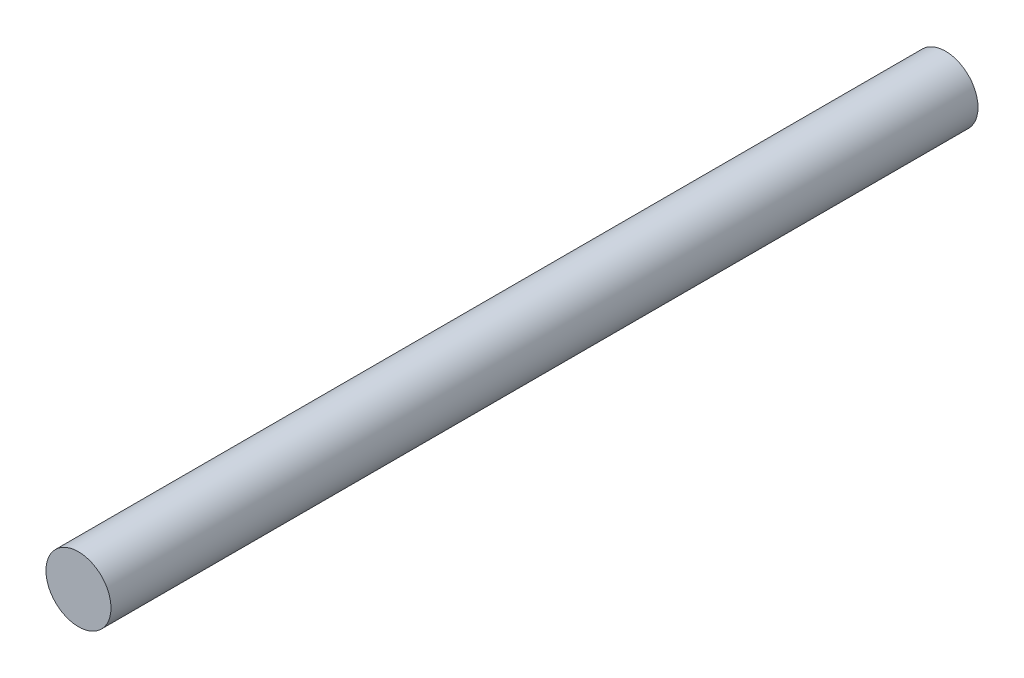
SolidWorks part; units mm, degrees
ref_plane "Front Plane" through (0, 0, 0) normal (0, 0, 1) x (1, 0, 0)
ref_plane "Top Plane" through (0, 0, 0) normal (0, 1, 0) x (1, 0, 0)
ref_plane "Right Plane" through (0, 0, 0) normal (1, 0, 0) x (0, 0, -1)
sketch "Sketch1" plane through (0, 0, 0) normal (0, 0, 1) x (1, 0, 0)
  circle A0 centre (0, 0) radius 3
  dimension "D1" = 6
extrude "Boss-Extrude1" add sketch "Sketch1" along normal blind 40 and the other way blind 40
